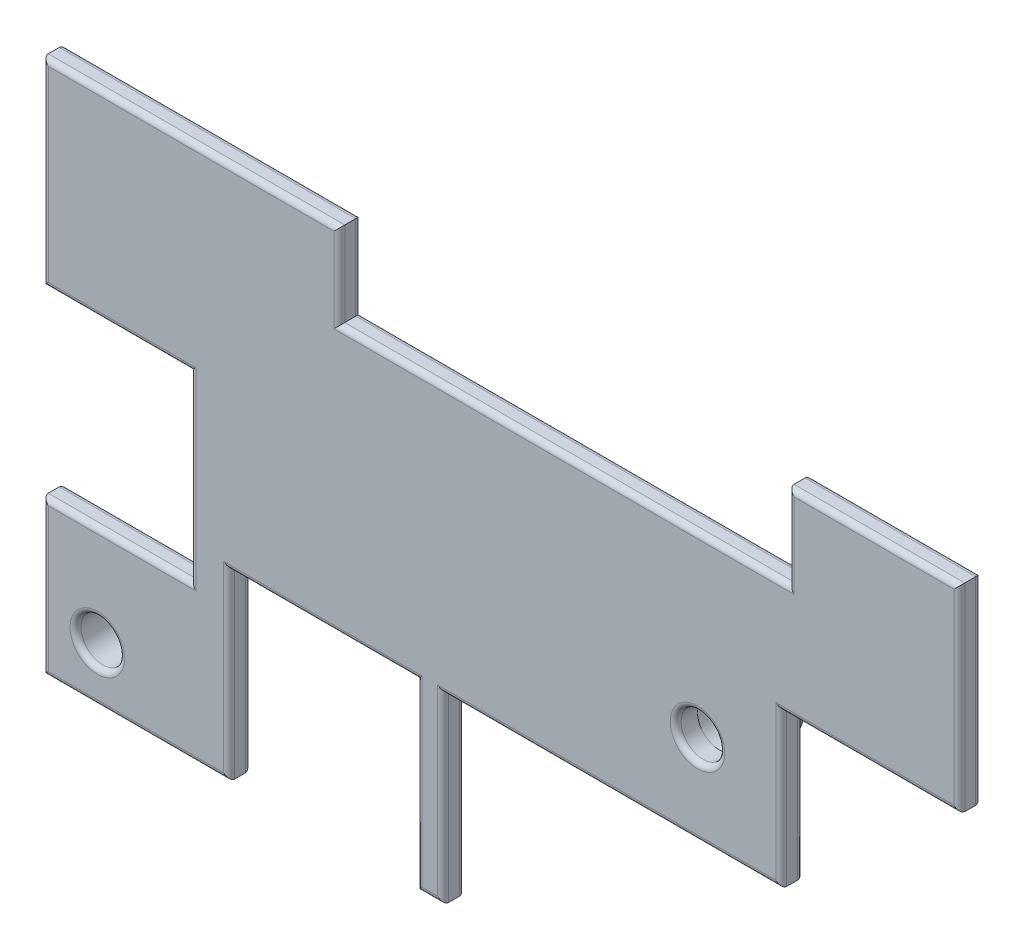
SolidWorks part; units mm, degrees
ref_plane "Front Plane" through (0, 0, 0) normal (1, 0, 0) x (0, 1, 0)
ref_plane "Top Plane" through (0, 0, 0) normal (0, 0, 1) x (0, 1, 0)
ref_plane "Right Plane" through (0, 0, 0) normal (0, 1, 0) x (-1, 0, 0)
sketch "Sketch1" plane through (0, 0, 0) normal (0, 0, 1) x (0, 1, 0)
  line L0 (-6.2603, 38.6703) -> (-6.2603, 25.151)
  line L2 (-20.4113, 38.6703) -> (-20.4113, 21.5903)
  line L3 (10.468, -45.3297) -> (28.6138, -45.3297)
  line L4 (28.6138, 38.6703) -> (28.6138, 11.4952)
  line L5 (-6.2603, 25.151) -> (10.468, 25.151)
  line L6 (10.468, 25.151) -> (10.468, 38.6703)
  line L7 (-20.4113, 38.6703) -> (-6.2603, 38.6703)
  line L8 (-20.3862, 38.6703) -> (28.6138, 38.6703) construction
  line L9 (10.468, 38.6703) -> (28.6138, 38.6703)
  line L10 (-20.4113, 21.5903) -> (-3.6328, 21.5903)
  line L11 (13.1138, 21.5903) -> (-17.8862, 21.5903) construction
  line L12 (-3.6328, 21.5903) -> (-3.6328, 4.3998)
  line L13 (-3.6328, 4.3998) -> (-20.4113, 4.3998)
  line L15 (-20.4113, 1.9897) -> (-3.6328, 1.9897)
  line L16 (-3.6328, 1.9897) -> (-3.6328, -15.0008)
  line L17 (28.6138, 11.4952) -> (20.8707, 11.4952)
  line L18 (-20.4113, 4.3998) -> (-20.4113, 1.9897)
  line L19 (20.8707, 11.4952) -> (20.8707, -29.6784)
  line L22 (-3.6328, -29.0068) -> (-3.6328, -15.0008)
  line L23 (20.8707, -29.6784) -> (28.6138, -29.6784)
  line L24 (28.6138, -29.6784) -> (28.6138, -45.3297)
  line L25 (10.468, -45.3297) -> (10.468, -29.0068)
  line L26 (10.468, -29.0068) -> (-3.6328, -29.0068)
  circle A0 centre (-15.3862, 33.6703) radius 2
  circle A1 centre (4.6138, -21.3297) radius 2
  dimension "D1" = 4
  dimension "D2" = 4
extrude "Boss-Extrude1" add sketch "Sketch1" along normal blind 2
sketch "Sketch3" plane through (0, 0, 0) normal (0, 0, -1) x (1, 0, 0)
  circle A5 centre (-33.6703, 15.3862) radius 2
  circle A6 centre (-33.6703, 15.3862) radius 3
  circle A8 centre (21.343, -4.6376) radius 2.1171
  circle A10 centre (21.343, -4.6376) radius 3.0333
  dimension "D1" = 6
extrude "Boss-Extrude2" add sketch "Sketch3" along normal blind 5
fillet "Fillet10" radius 0.5 46 edges at (18.3097, 4.6376, -5) (-36.6703, -15.3862, -5) (23.3297, 4.6138, 2) (-31.6703, -15.3862, 2) (-31.9106, -6.2603, 2) (-25.151, 2.1038, 2) (-31.9106, 10.468, 2) (-38.6703, 19.5409, 2) (-25.0827, 28.6138, 2) (-11.4952, 24.7422, 2) (9.0916, 20.8707, 2) (29.6784, 24.7422, 2) (37.5041, 28.6138, 2) (45.3297, 19.5409, 2) (37.1683, 10.468, 2) (29.0068, 3.4176, 2) (13.5086, -3.6328, 2) (-1.9897, -12.022, 2) (-3.1948, -20.4113, 2) (-4.3998, -12.022, 2) (-12.995, -3.6328, 2) (-21.5903, -12.022, 2) (-30.1303, -20.4113, 2) (-38.6703, -13.3358, 2) (-30.1303, -20.4113, 0) (-21.5903, -12.022, 0) (-12.995, -3.6328, 0) (-4.3998, -12.022, 0) (-3.1948, -20.4113, 0) (-1.9897, -12.022, 0) (13.5086, -3.6328, 0) (29.0068, 3.4176, 0) (37.1683, 10.468, 0) (45.3297, 19.5409, 0) (37.5041, 28.6138, 0) (29.6784, 24.7422, 0) (9.0916, 20.8707, 0) (-11.4952, 24.7422, 0) (-25.0827, 28.6138, 0) (-38.6703, 19.5409, 0) (-31.9106, 10.468, 0) (-25.151, 2.1038, 0) (-31.9106, -6.2603, 0) (-38.6703, -13.3358, 0) (18.3097, 4.6376, 0) (-36.6703, -15.3862, 0)
